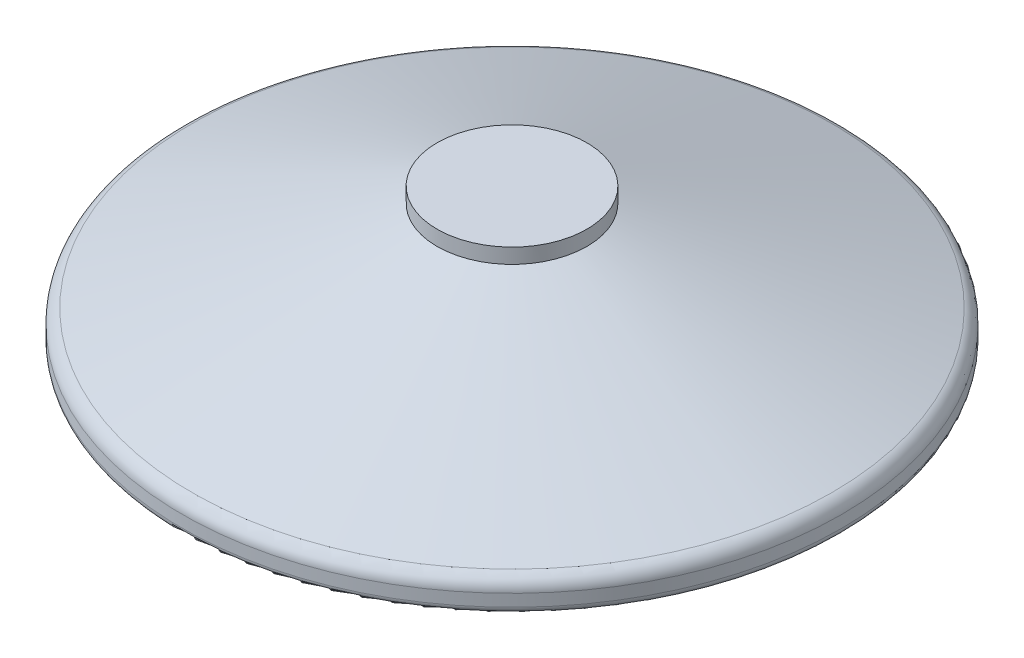
SolidWorks part; units mm, degrees
ref_plane "Front Plane" through (0, 0, 0) normal (0, 0, 1) x (1, 0, 0)
ref_plane "Top Plane" through (0, 0, 0) normal (0, 1, 0) x (1, 0, 0)
ref_plane "Right Plane" through (0, 0, 0) normal (1, 0, 0) x (0, 0, -1)
sketch "Sketch1" plane through (0, 0, 0) normal (0, 0, 1) x (1, 0, 0)
  line L0 (0, 57.0536) -> (0, 9.3) construction
  line L1 (-6, 4.1532) -> (-21.5, 0)
  line L2 (-21.5, 0) -> (-22, 0)
  line L3 (-22, 0) -> (-22, 2)
  line L4 (-22, 2) -> (-5, 8.3)
  line L5 (-5, 8.3) -> (-5, 9.3)
  line L6 (-5, 9.3) -> (0, 9.3)
  line L7 (0, 0) -> (-21.5, 0) construction
  line L8 (0, 9.3) -> (0, 4.1532)
  line L9 (-6, 4.1532) -> (0, 4.1532)
  line L10 (0, 9.3) -> (0, -21.875) construction
  dimension "D1" = 10
  dimension "D2" = 44
  dimension "D3" = 9.3
  dimension "D4" = 165
  dimension "D5" = 0.5
  dimension "D6" = 2
  dimension "D7" = 5.5646
  dimension "D8" = 15
  dimension "D9" = 1
  dimension "D10" = 12
revolve "Revolve1" add sketch "Sketch1" angle 360 about L0
fillet "Fillet1" radius 1 1 edges at (-22, 2, 0)
fillet "Fillet2" radius 0.5 1 edges at (-22, 0, 0)
